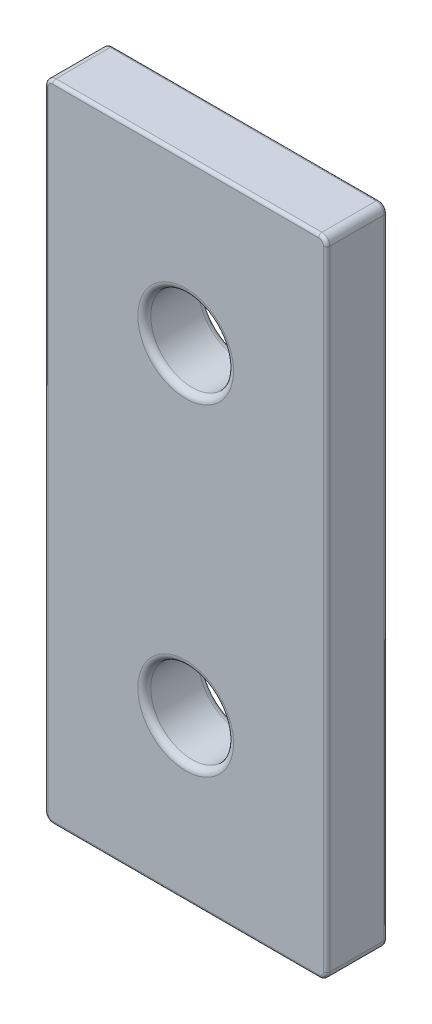
SolidWorks part; units mm, degrees
ref_plane "Front Plane" through (0, 0, 0) normal (0, 0, 1) x (1, 0, 0)
ref_plane "Top Plane" through (0, 0, 0) normal (0, 1, 0) x (1, 0, 0)
ref_plane "Right Plane" through (0, 0, 0) normal (1, 0, 0) x (0, 0, -1)
sketch "Sketch1" plane through (0, 0, 0) normal (0, 0, 1) x (1, 0, 0)
  line L0 (-11.1125, 25.4) -> (-11.1125, -25.4)
  line L1 (-11.1125, 25.4) -> (11.1125, 25.4)
  line L2 (-11.1125, -25.4) -> (11.1125, -25.4)
  line L3 (11.1125, 25.4) -> (11.1125, -25.4)
  line L4 (-11.1125, 0) -> (11.1125, 0) construction
  line L5 (0, -12.7) -> (0, 12.7) construction
  line L6 (-3.175, 12.7) -> (-1.905, 12.7) construction
  circle A0 centre (0, 12.7) radius 3.2639
  circle A2 centre (0, 12.7) radius 3.175 construction
  circle A3 centre (25.4, 12.7) radius 3.2639
  circle A4 centre (25.4, -12.7) radius 3.2639
  circle A5 centre (0, -12.7) radius 3.2639
  dimension "Thru Hole Diameter" = 6.5278
  dimension "Mounting Fastener Thread Size" = 6.35
  dimension "Width" = 22.225
  dimension "Length" = 50.8
  dimension "Mounting Hole Vert CtoC" = 25.4
  dimension "Mounting Fastener Thread Pitch" = 1.27
  dimension "D1" = 12.7
  dimension "D2" = 11.1125
  dimension "Mounting Hole Horiz CtoC" = 25.4
  dimension "Mounting Hole Vertical Offset" = 12.7
  dimension "Mounting Hole Horizontal Offset" = 11.1125
  dimension "D50" = 2
  dimension "Number of Vertical Holes" = 2
sketch "Sketch2" plane through (0, 0, 0) normal (1, 0, 0) x (0, 0, -1)
  line L0 (-2.3876, 12.7) -> (2.3876, 12.7) construction
  line L1 (2.3876, 12.7) -> (15.0749, 12.7) construction
  dimension "Thickness" = 4.7752
  dimension "Mounting Fastener Thread Length" = 17.4625
sketch "Sketch3" plane through (0, 0, 0) normal (0, 0, 1) x (1, 0, 0)
  line L0 (-11.1125, 25.4) -> (-11.1125, -25.4) construction
  line L1 (-11.1125, -25.4) -> (11.1125, -25.4) construction
  line L2 (11.1125, 25.4) -> (11.1125, -25.4) construction
  line L3 (-11.1125, 25.4) -> (11.1125, 25.4) construction
  line L4 (-11.1125, 25.4) -> (-11.1125, -25.4)
  line L5 (-11.1125, -25.4) -> (11.1125, -25.4)
  line L6 (11.1125, 25.4) -> (11.1125, -25.4)
  line L7 (-11.1125, 25.4) -> (11.1125, 25.4)
extrude "Boss-Extrude1" add sketch "Sketch3" along normal up to vertex (2.3876 mm away) from vertex up to point (0, 12.7, 2.3876) starting at point (0, 12.7, -2.3876)
fillet "Fillet1" radius 0.635 4 edges at (11.1125, -25.4, 0) (-11.1125, -25.4, 0) (-11.1125, 25.4, 0) (11.1125, 25.4, 0)
sketch "Sketch4" plane through (0, 0, 2.3876) normal (0, 0, 1) x (1, 0, 0)
  circle A0 centre (0, 12.7) radius 3.2639 construction
  circle A1 centre (0, 12.7) radius 3.2639
extrude "Cut-Extrude1" cut sketch "Sketch4" against normal through all
pattern_linear "LPattern1" count 2 spacing 25.4 along (0, -1, 0) count 2 spacing 25.4 along (1, 0, 0) of "Cut-Extrude1"
fillet "Fillet2" radius 0.254 16 edges at (10.9265, -25.214, -2.3876) (0, -25.4, -2.3876) (-10.9265, -25.214, -2.3876) (-11.1125, 0, -2.3876) (-10.9265, 25.214, -2.3876) (0, 25.4, -2.3876) (10.9265, 25.214, -2.3876) (10.9265, -25.214, 2.3876) (0, -25.4, 2.3876) (-10.9265, -25.214, 2.3876) (-11.1125, 0, 2.3876) (-10.9265, 25.214, 2.3876) (0, 25.4, 2.3876) (10.9265, 25.214, 2.3876) (11.1125, 0, -2.3876) (11.1125, 0, 2.3876)
fillet "Fillet3" radius 0.508 4 edges at (3.2639, 12.7, -2.3876) (3.2639, -12.7, -2.3876) (3.2639, 12.7, 2.3876) (3.2639, -12.7, 2.3876)
equation "\"D1@LPattern1\"=\"Number of Vertical Holes@Sketch1\""
equation "\"D4@LPattern1\"=\"D3@LPattern1\""
equation "\"D3@LPattern1\"=\"Mounting Hole Vert CtoC@Sketch1\""
equation "\"Mounting Hole Horiz CtoC@Sketch1\"=\"Mounting Hole Vert CtoC@Sketch1\""
